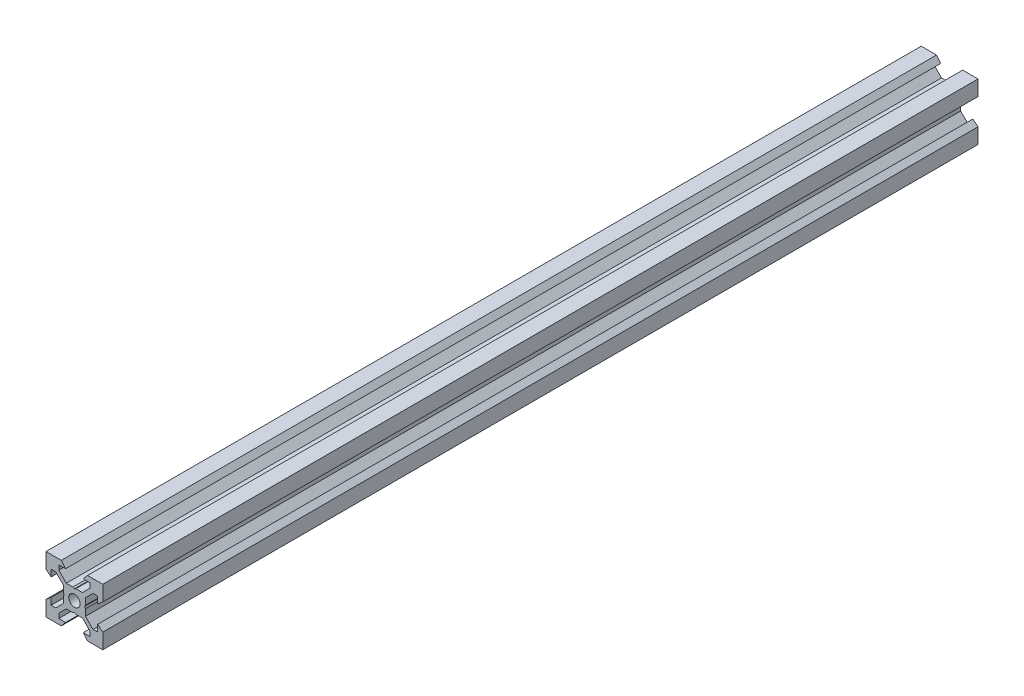
SolidWorks part; units mm, degrees
ref_plane "Front Plane" through (0, 0, 0) normal (0, 0, 1) x (1, 0, 0)
ref_plane "Top Plane" through (0, 0, 0) normal (0, 1, 0) x (1, 0, 0)
ref_plane "Right Plane" through (0, 0, 0) normal (1, 0, 0) x (0, 0, -1)
sketch "Sketch1" plane through (0, 0, 0) normal (0, 0, 1) x (1, 0, 0)
  line L0 (10, 10) -> (4.6104, 10) construction
  line L1 (10, 10) -> (10, 4.6104) construction
  line L2 (10, -10) -> (10, -4.6104) construction
  line L3 (10, -10) -> (4.6104, -10) construction
  line L4 (10, 10) -> (10, 4.6104)
  line L5 (6.5607, 5.5) -> (8.2, 5.5)
  line L6 (5.5, 8.2) -> (5.5, 6.5607)
  line L7 (10, 10) -> (4.6104, 10)
  line L8 (10, 10) -> (10, 4.6104)
  line L9 (6.5607, 5.5) -> (3.9, 2.8393)
  line L10 (5.5, 6.5607) -> (2.8393, 3.9)
  line L11 (10, 4.6104) -> (8.2, 3.1)
  line L12 (4.6104, 10) -> (3.1, 8.2)
  line L13 (8.2, 3.1) -> (8.2, 5.5)
  line L14 (3.1, 8.2) -> (5.5, 8.2)
  line L15 (-6.5607, 5.5) -> (-8.2, 5.5)
  line L16 (6.5607, -5.5) -> (8.2, -5.5)
  line L17 (3.1, -8.2) -> (5.5, -8.2)
  line L18 (8.2, -3.1) -> (8.2, -5.5)
  line L19 (4.6104, -10) -> (3.1, -8.2)
  line L20 (10, -4.6104) -> (8.2, -3.1)
  line L21 (0.5196, -3.9) -> (0, -3.6)
  line L22 (0.5196, 3.9) -> (0, 3.6)
  line L23 (3.6, 0) -> (3.9, -0.5196)
  line L24 (3.9, 0.5196) -> (3.6, 0)
  line L25 (3.9, 0.5196) -> (3.9, 2.8393)
  line L26 (2.8393, 3.9) -> (0.5196, 3.9)
  line L27 (3.9, -2.8393) -> (3.9, -0.5196)
  line L28 (2.8393, -3.9) -> (0.5196, -3.9)
  line L29 (5.5, -6.5607) -> (2.8393, -3.9)
  line L30 (6.5607, -5.5) -> (3.9, -2.8393)
  line L31 (10, -10) -> (10, -4.6104)
  line L32 (10, -10) -> (4.6104, -10)
  line L33 (5.5, -8.2) -> (5.5, -6.5607)
  line L34 (-6.5607, -5.5) -> (-8.2, -5.5)
  line L35 (10, -10) -> (10, -4.6104)
  line L36 (0, 0) -> (0, 8.2) construction
  line L37 (-10, -10) -> (-4.6104, -10) construction
  line L38 (-10, -10) -> (-10, -4.6104) construction
  line L39 (-10, 10) -> (-10, 4.6104) construction
  line L40 (-10, 10) -> (-4.6104, 10) construction
  line L41 (-10, -10) -> (-10, -4.6104)
  line L43 (-5.5, -8.2) -> (-5.5, -6.5607)
  line L44 (-10, -10) -> (-4.6104, -10)
  line L45 (-10, -10) -> (-10, -4.6104)
  line L46 (-6.5607, -5.5) -> (-3.9, -2.8393)
  line L47 (-5.5, -6.5607) -> (-2.8393, -3.9)
  line L48 (-2.8393, -3.9) -> (-0.5196, -3.9)
  line L49 (-3.9, -2.8393) -> (-3.9, -0.5196)
  line L50 (-2.8393, 3.9) -> (-0.5196, 3.9)
  line L51 (-3.9, 0.5196) -> (-3.9, 2.8393)
  line L52 (-3.9, 0.5196) -> (-3.6, 0)
  line L53 (-3.6, 0) -> (-3.9, -0.5196)
  line L54 (-0.5196, 3.9) -> (0, 3.6)
  line L55 (-0.5196, -3.9) -> (0, -3.6)
  line L56 (-10, -4.6104) -> (-8.2, -3.1)
  line L57 (-4.6104, -10) -> (-3.1, -8.2)
  line L58 (-8.2, -3.1) -> (-8.2, -5.5)
  line L59 (-3.1, -8.2) -> (-5.5, -8.2)
  line L60 (-10, -10) -> (10, -10) construction
  line L61 (-10, -10) -> (-10, 10) construction
  line L62 (-3.1, 8.2) -> (-5.5, 8.2)
  line L63 (-8.2, 3.1) -> (-8.2, 5.5)
  line L64 (-4.6104, 10) -> (-3.1, 8.2)
  line L65 (-10, 4.6104) -> (-8.2, 3.1)
  line L66 (-5.5, 6.5607) -> (-2.8393, 3.9)
  line L67 (-6.5607, 5.5) -> (-3.9, 2.8393)
  line L68 (-10, 10) -> (-10, 4.6104)
  line L69 (-10, 10) -> (-4.6104, 10)
  line L70 (-5.5, 8.2) -> (-5.5, 6.5607)
  line L71 (-10, 10) -> (10, 10) construction
  line L72 (-10, 10) -> (-10, 4.6104)
  line L73 (10, -10) -> (10, 10) construction
  line L74 (-10, -10) -> (10, 10) construction
  line L75 (-10, 10) -> (10, -10) construction
  circle A0 centre (0, 0) radius 2
  dimension "D7" = 4
  dimension "D1" = 20
  dimension "D2" = 5.3896
  dimension "D3" = 4.5
  dimension "D4" = 50
  dimension "D5" = 1.8
  dimension "D6" = 1.5104
  dimension "D8" = 5.5
  dimension "D9" = 120
  dimension "D10" = 0.3
  dimension "D11" = 2.3197
  dimension "D12" = 7.8
  dimension "D13" = 7.8
  dimension "D14" = 1.5
  dimension "D15" = 2.6607
extrude "Boss-Extrude1" add sketch "Sketch1" along normal mid plane 308.33 contours L70 L62 L64 L69 L68 L65 L63 L15 L67 L51 L52 L53 L49 L46 L34 L58 L56 L41 L44 L57 L59 L43 L47 L48 L55 L21 L28 L29 L33 L17 L19 L32 L31 L20 L18 L16 L30 L27 L23 L24 L25 L9 L5 L13 L11 L4 L7 L12 L14 L6 L10 region at (9.7172, 7.3052, 0)
